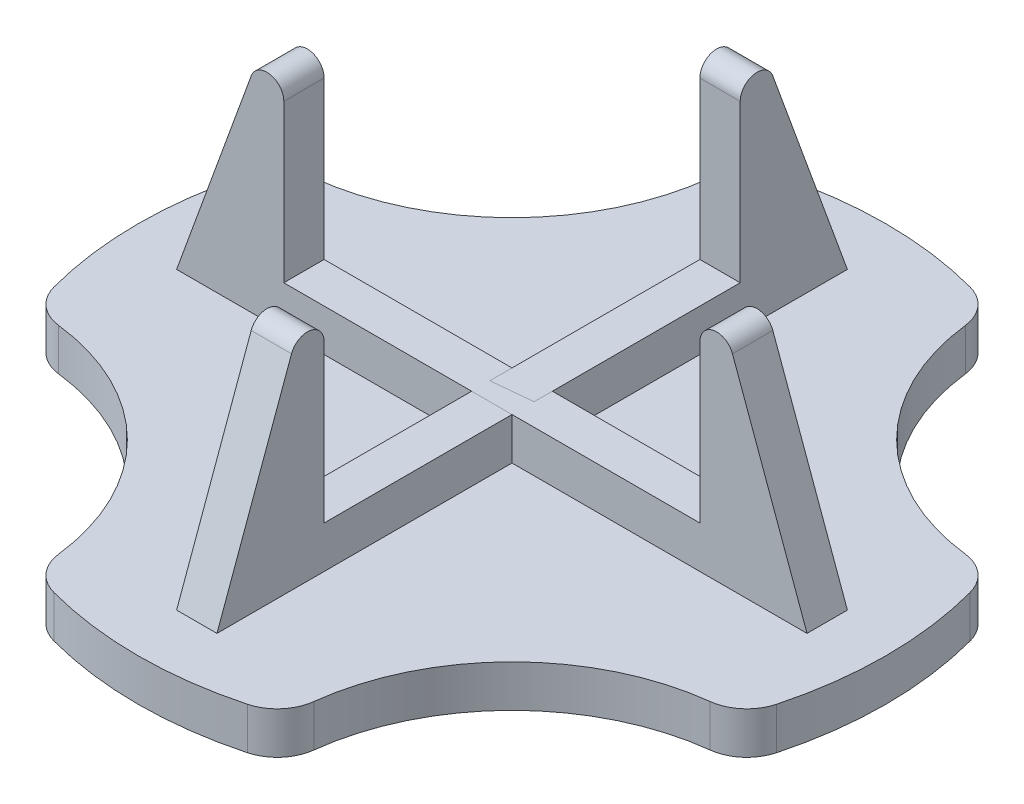
SolidWorks part; units mm, degrees
ref_plane "Front Plane" through (0, 0, 0) normal (0, 0, 1) x (1, 0, 0)
ref_plane "Top Plane" through (0, 0, 0) normal (0, 1, 0) x (1, 0, 0)
ref_plane "Right Plane" through (0, 0, 0) normal (1, 0, 0) x (0, 0, -1)
sketch "Sketch1" plane through (0, 0, 0) normal (0, 1, 0) x (1, 0, 0)
  line L1 (31.9917, -3.048) -> (-31.9917, -3.048)
  line L2 (31.9917, -3.048) -> (31.9917, 3.048)
  line L3 (31.9917, 3.048) -> (-31.9917, 3.048)
  line L4 (-31.9917, -3.048) -> (-31.9917, 3.048)
  line L5 (31.9917, -3.048) -> (-31.9917, 3.048) construction
  line L6 (31.9917, 3.048) -> (-31.9917, -3.048) construction
  circle A0 centre (0, 0) radius 56.515
  dimension "D1" = 113.03
  dimension "D2" = 6.096
extrude "Boss-Extrude1" add sketch "Sketch1" along normal blind 6.35
sketch "Sketch2" plane through (0, 0, 0) normal (0, 0, 1) x (1, 0, 0)
  line L0 (0, -978.17) -> (0, 49021.83) construction
  line L1 (-47.625, 6.35) -> (-36.3593, 37.3022)
  line L2 (-31.4325, 36.4335) -> (-31.4325, 12.7)
  line L3 (-31.4325, 12.7) -> (31.4325, 12.7)
  line L4 (31.4325, 12.7) -> (31.4325, 36.4335)
  line L5 (36.3593, 37.3022) -> (47.625, 6.35)
  line L6 (-47.625, 6.35) -> (-47.625, 0)
  line L7 (-33.9725, 36.4335) -> (33.9725, 36.4335) construction
  line L9 (62.1665, 0) -> (-62.1665, 0) construction
  line L10 (-47.625, 0) -> (47.625, 0)
  line L11 (47.625, 0) -> (47.625, 6.35)
  line L13 (-56.515, 0) -> (56.515, 0) construction
  line L14 (56.515, 6.35) -> (-56.515, 6.35) construction
  arc A0 (-31.4325, 36.4335) -> (-36.3593, 37.3022) centre (-33.9725, 36.4335) ccw
  arc A1 (36.3593, 37.3022) -> (31.4325, 36.4335) centre (33.9725, 36.4335) ccw
  dimension "D4" = 2.54
  dimension "D1" = 62.865
  dimension "D2" = 95.25
  dimension "D3" = 12.7
  dimension "D5" = 70
extrude "Boss-Extrude2" add sketch "Sketch2" along normal mid plane 6.096 separate body
ref_axis "Axis1" through (0, 53.34, 0) along (0, -1, 0)
pattern_circular "CirPattern1" count 2 every 90 about axis through (0, 53.34, 0) along (0, -1, 0) of bodies 102
sketch "Sketch3" plane through (0, 0, 0) normal (0, 1, 0) x (1, 0, 0)
  line L0 (-53.2075, 53.2075) -> (0, 0) construction
  line L1 (-55, 0) -> (55, 0) construction
  line L2 (-53.2075, 19.05) -> (-19.05, 19.05) construction
  line L3 (-19.05, 19.05) -> (-19.05, 53.2075) construction
  circle A0 centre (-53.2075, 53.2075) radius 34.1575
  circle A1 centre (0, 0) radius 56.515 construction
  dimension "D1" = 45
  dimension "D2" = 19.05
extrude "Cut-Extrude1" cut sketch "Sketch3" along normal through all
fillet "Fillet1" radius 6.35 2 edges at (-53.2075, 3.175, -19.05) (-19.05, 3.175, -53.2075)
pattern_circular "CirPattern2" count 4 over 360 about axis through (0, 53.34, 0) along (0, -1, 0) of "Cut-Extrude1", "Fillet1"
